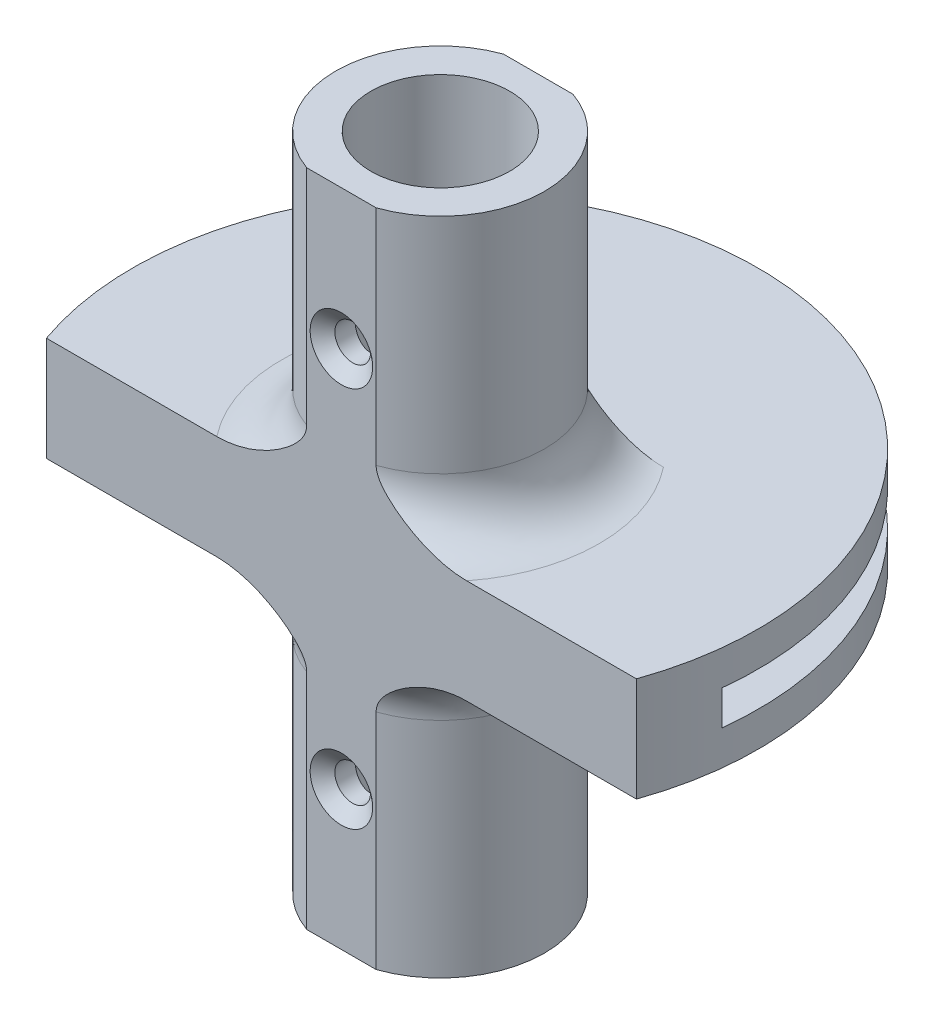
SolidWorks part; units mm, degrees
material "ABS"
ref_plane "Front Plane" through (0, 0, 0) normal (0, 0, 1) x (1, 0, 0)
ref_plane "Top Plane" through (0, 0, 0) normal (0, 1, 0) x (1, 0, 0)
ref_plane "Right Plane" through (0, 0, 0) normal (1, 0, 0) x (0, 0, -1)
sketch "Sketch3" plane through (0, 0, 0) normal (0, 1, 0) x (1, 0, 0)
  line L8 (0, 28.6) -> (0, -28.6) construction
  line L9 (0, 28.6) -> (0, -9.5) construction
  line L10 (-26.976, -9.5) -> (26.976, -9.5)
  line L11 (-28.4259, -3.15) -> (28.4259, -3.15)
  arc A4 (26.976, -9.5) -> (-26.976, -9.5) centre (0, 0) ccw
  point P9 (0, 0)
  dimension "D1" = 38.1
  dimension "D2" = 6.35
extrude "Boss-Extrude1" add sketch "Sketch3" along normal blind 3.175 contours L11 A4 | L10 A4 L11
sketch "Sketch18" plane through (0, 0, 0) normal (0, 1, 0) x (1, 0, 0)
  spline S0 degree 3 poles (7.5796, 9.5576) (2.8196, 9.5576) (-1.9436, 9.5576) (-6.7079, 9.5576) knots 3 3 3 3 4 4 4 4
  spline S1 degree 3 poles (7.5796, 23.8479) (7.5796, 19.0863) (7.5796, 14.322) (7.5796, 9.5576) knots 2 2 2 2 3 3 3 3
  spline S2 degree 3 poles (-6.7079, 23.8479) (-1.9477, 23.8479) (2.8137, 23.8479) (7.5796, 23.8479) knots 1 1 1 1 2 2 2 2
  spline S3 degree 3 poles (-6.7079, 9.5576) (-6.7079, 14.3201) (-6.7079, 19.0826) (-6.7079, 23.8479) knots 0 0 0 0 1 1 1 1
  spline S4 degree 3 poles (3.4908, 19.7615) (3.4639, 19.7638) (3.4462, 19.7666) (3.4285, 19.7666) (1.4101, 19.7661) (-0.6084, 19.7654) (-2.6268, 19.7647) knots 12 12 12 12 13 13 13 14 14 14 14
  spline S5 degree 3 poles (3.4908, 13.6518) (3.4908, 15.6921) (3.4908, 17.7258) (3.4908, 19.7615) knots 11 11 11 11 12 12 12 12
  spline S6 degree 3 poles (-2.6269, 13.6437) (-0.6039, 13.6431) (1.419, 13.6424) (3.442, 13.6422) (3.4587, 13.6422) (3.4754, 13.6486) (3.4908, 13.6518) knots 9 9 9 9 10 10 10 11 11 11 11
  spline S7 degree 3 poles (-2.6269, 11.6094) (-2.6269, 12.2941) (-2.6269, 12.9689) (-2.6269, 13.6437) knots 8 8 8 8 9 9 9 9
  spline S8 degree 3 poles (-4.6581, 11.6094) (-3.9766, 11.6094) (-3.3042, 11.6094) (-2.6269, 11.6094) knots 7 7 7 7 8 8 8 8
  spline S9 degree 3 poles (-4.6581, 13.6399) (-4.6581, 12.9525) (-4.6581, 12.2802) (-4.6581, 11.6094) knots 6 6 6 6 7 7 7 7
  spline S10 degree 3 poles (-2.623, 13.6399) (-3.3011, 13.6399) (-3.9791, 13.6399) (-4.6581, 13.6399) knots 5 5 5 5 6 6 6 6
  spline S11 degree 3 poles (-2.6229, 19.7686) (-2.623, 17.7257) (-2.623, 15.6828) (-2.623, 13.6399) knots 4 4 4 4 5 5 5 5
  spline S12 degree 3 poles (-4.6572, 19.7686) (-3.9725, 19.7686) (-3.2977, 19.7686) (-2.6229, 19.7686) knots 3 3 3 3 4 4 4 4
  spline S13 degree 3 poles (-4.6572, 21.7998) (-4.6572, 21.1183) (-4.6572, 20.4459) (-4.6572, 19.7686) knots 2 2 2 2 3 3 3 3
  spline S14 degree 3 poles (-2.6268, 21.7998) (-3.3141, 21.7998) (-3.9864, 21.7998) (-4.6572, 21.7998) knots 1 1 1 1 2 2 2 2
  spline S15 degree 3 poles (-2.6268, 19.7647) (-2.6268, 20.4427) (-2.6268, 21.1208) (-2.6268, 21.7998) knots 0 0 0 0 1 1 1 1
sketch "Sketch19" plane through (0, 0, 0) normal (0, 1, 0) x (1, 0, 0)
  line L3 (-3.175, 8.4947) -> (3.175, 8.4947)
  line L4 (-3.175, -9.5) -> (3.175, -9.5)
  arc A3 (3.175, -9.5) -> (3.175, 8.4947) centre (0.0442, -0.5026) ccw
  arc A4 (-3.175, 8.4947) -> (-3.175, -9.5) centre (0.0442, -0.5026) ccw
  circle A5 centre (0.0442, -0.5026) radius 6.35
  point P0 (4.5522, 7.2704)
  point P2 (0, 0)
  point P10 (0, 8.4947)
  point P11 (0, -9.5)
  point P13 (0, 0)
  point P16 (-12.8694, 25.4)
  point P17 (0, 0)
  point P18 (0, 0)
  point P19 (0, 0)
  point P20 (0, 0)
  dimension "D1" = 12.7
  dimension "D2" = 3.1765
  dimension "D3" = 3.2059
  dimension "D4" = 6.35
extrude "Boss-Extrude2" add sketch "Sketch19" against normal blind 25.4 contours L3 A4 A5 | L3 A5 L4 A3 region at (0, 0, -8.2324)
ref_plane "Plane2" through (0, 3.175, 0) normal (0, 1, 0) x (1, 0, 0)
sketch "Sketch20" plane through (0, 3.175, 0) normal (0, 1, 0) x (1, 0, 0)
  line L0 (-28.4259, -3.15) -> (28.4259, -3.15) construction
  line L1 (-26.976, -9.5) -> (26.976, -9.5) construction
  line L2 (-28.4259, -3.15) -> (28.4259, -3.15)
  line L3 (-26.976, -9.5) -> (26.976, -9.5)
  arc A0 (26.976, -9.5) -> (-26.976, -9.5) centre (0, 0) ccw construction
  arc A1 (26.976, -9.5) -> (28.4259, -3.15) centre (0, 0) ccw
  arc A2 (-28.4259, -3.15) -> (-26.976, -9.5) centre (0, 0) ccw
extrude "Boss-Extrude3" add sketch "Sketch20" along normal blind 3.175
ref_plane "Plane3" through (0, 6.35, 0) normal (0, 1, 0) x (1, 0, 0)
sketch "Sketch21" plane through (0, 6.35, 0) normal (0, 1, 0) x (1, 0, 0)
  line L0 (-26.976, -9.5) -> (26.976, -9.5)
  arc A0 (26.976, -9.5) -> (-26.976, -9.5) centre (0, 0) ccw construction
  arc A1 (26.976, -9.5) -> (-26.976, -9.5) centre (0, 0) ccw
extrude "Boss-Extrude4" add sketch "Sketch21" along normal blind 3.175
ref_plane "Plane4" through (0, 9.525, 0) normal (0, 1, 0) x (1, 0, 0)
sketch "Sketch23" plane through (0, 9.525, 0) normal (0, 1, 0) x (1, 0, 0)
  line L0 (-26.976, -9.5) -> (26.976, -9.5) construction
  line L1 (-3.175, 8.4947) -> (3.175, 8.4947) construction
  line L2 (-3.175, -9.5) -> (3.175, -9.5)
  line L3 (-3.175, 8.4947) -> (3.175, 8.4947)
  circle A0 centre (0.0442, -0.5026) radius 6.35 construction
  arc A1 (-3.175, 8.4947) -> (-3.175, -9.5) centre (0.0442, -0.5026) ccw construction
  arc A2 (3.175, -9.5) -> (3.175, 8.4947) centre (0.0442, -0.5026) ccw construction
  circle A3 centre (0.0442, -0.5026) radius 6.35
  arc A4 (-3.175, 8.4947) -> (-3.175, -9.5) centre (0.0442, -0.5026) ccw
  arc A5 (3.175, -9.5) -> (3.175, 8.4947) centre (0.0442, -0.5026) ccw
extrude "Boss-Extrude5" add sketch "Sketch23" along normal blind 25.4
hole_wizard "CSK for #4 Flat Head Machine Screw (100)1" positions "Sketch24" profile "Sketch25" countersink size "#4" standard "ANSI Inch" end condition up to next
sketch "Sketch24" plane through (0, 0, 9.5) normal (0, 0, 1) x (1, 0, 0)
  line L4 (0, -25.4) -> (0, 0) construction
  line L5 (-3.175, -25.4) -> (3.175, -25.4) construction
  line L7 (0, 9.433) -> (0, 34.925) construction
  line L8 (-3.175, 34.925) -> (3.175, 34.925) construction
  point P0 (0, -12.7)
  point P2 (0, 22.179)
  point P28 (0, 0)
  point P29 (0, 0)
sketch "Sketch25" plane through (0, -12.7, 9.5) normal (1, 0, 0) x (0, -1, 0)
  line L0 (0, 0) -> (0, 2.6475)
  line L1 (0, 2.6475) -> (1.6319, 2.6475)
  line L2 (1.6319, 2.6475) -> (1.6319, 1.0284)
  line L3 (1.6319, 1.0284) -> (2.8575, 0)
  line L5 (2.8575, 0) -> (0, 0)
  line L6 (-1.632, 1.0284) -> (-2.8575, 0) construction
  line L11 (0, -6.35) -> (0, 107.95) construction
  dimension "Thru Hole Dia." = 3.2639
  dimension "Thru Hole Depth" = 2.6475
  dimension "Near C'Sink Dia." = 5.715
  dimension "Near C'Sink Angle" = 100
hole_wizard "CSK for #4 Flat Head Machine Screw (100)2" positions "Sketch26" profile "Sketch27" countersink size "#4" standard "ANSI Inch" end condition up to next
sketch "Sketch26" plane through (0, 0, 0) normal (0, -1, 0) x (-1, 0, 0)
  line L3 (27.0462, 9.2981) -> (0, 9.2981) construction
  line L4 (0, 9.2981) -> (-27.0462, 9.2981) construction
  line L7 (0, 28.6) -> (0, -28.6) construction
  arc A0 (26.976, -9.5) -> (-26.976, -9.5) centre (0, 0) ccw construction
  arc A1 (26.976, -9.5) -> (-26.976, -9.5) centre (0, 0) ccw
  point P0 (13.5231, 9.2981)
  point P2 (-13.5231, 9.2981)
  point P24 (0, 0)
  point P25 (0, 0)
  point P26 (0, 0)
  point P27 (-28.4801, 7.2219)
  point P31 (0, 0)
  point P32 (0, 0)
  point P33 (0, 0)
  point P40 (0, 18.691)
sketch "Sketch27" plane through (-13.5231, 0, -9.2981) normal (1, 0, 0) x (0, 0, -1)
  line L0 (0, 0) -> (0, 3.175)
  line L1 (0, 3.175) -> (1.6319, 3.175)
  line L2 (1.6319, 3.175) -> (1.6319, 1.0284)
  line L3 (1.6319, 1.0284) -> (2.8575, 0)
  line L5 (2.8575, 0) -> (0, 0)
  line L6 (-1.6319, 1.0284) -> (-2.8575, 0) construction
  line L11 (0, -6.35) -> (0, 107.95) construction
  dimension "Thru Hole Dia." = 3.2639
  dimension "Thru Hole Depth" = 3.175
  dimension "Near C'Sink Dia." = 5.715
  dimension "Near C'Sink Angle" = 100
fillet "Fillet1" radius 5 4 edges at (-9.5117, 0, 0.5026) (9.5707, 0, 0.5026) (-9.5117, 9.525, 0.5026) (9.5707, 9.525, 0.5026)
